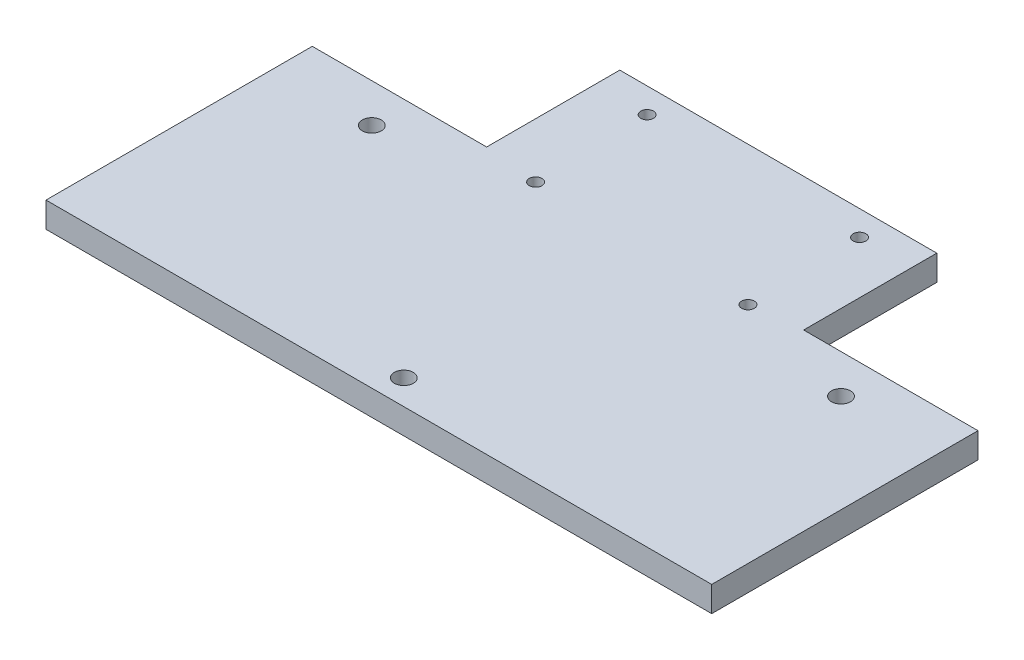
SolidWorks part; units mm, degrees
ref_plane "Front Plane" through (0, 0, 0) normal (0, 0, 1) x (1, 0, 0)
ref_plane "Top Plane" through (0, 0, 0) normal (0, 1, 0) x (1, 0, 0)
ref_plane "Right Plane" through (0, 0, 0) normal (1, 0, 0) x (0, 0, -1)
sketch "Sketch1" plane through (0, 0, 0) normal (0, 1, 0) x (1, 0, 0)
  line L0 (-47.6178, 3.1383) -> (57.3822, 3.1383) construction
  line L1 (-47.6178, 13.1383) -> (-20.1178, 13.1383)
  line L2 (-47.6178, 13.1383) -> (-47.6178, -28.8617)
  line L3 (-47.6178, -28.8617) -> (57.3822, -28.8617)
  line L4 (57.3822, 13.1383) -> (57.3822, -28.8617)
  line L5 (-47.6178, -18.8617) -> (57.3822, -18.8617) construction
  line L6 (-47.6178, -7.8617) -> (57.3822, -7.8617) construction
  line L7 (4.8822, 11.1383) -> (4.8822, -28.8617) construction
  line L8 (-20.1178, 13.1383) -> (-20.1178, 34.1383)
  line L9 (-20.1178, 34.1383) -> (29.8822, 34.1383)
  line L10 (29.8822, 34.1383) -> (29.8822, 13.1383)
  line L11 (29.8822, 13.1383) -> (57.3822, 13.1383)
  line L12 (4.8822, 34.1383) -> (4.8822, 11.1383) construction
  circle A0 centre (-32.1178, 7.0284) radius 1.5
  circle A1 centre (41.8822, 7.0284) radius 1.5
  circle A2 centre (4.8822, -24.9268) radius 1.5
  circle A3 centre (-11.8678, 30.2027) radius 1
  circle A4 centre (21.6322, 30.2027) radius 1
  circle A5 centre (-11.4651, 12.2072) radius 1
  circle A6 centre (22.0349, 12.2072) radius 1
  point P31 (21.6322, 30.2027)
  point P32 (0, 0)
  point P33 (0, 0)
  dimension "D5" = 37
  dimension "D6" = 3
  dimension "D7" = 50
  dimension "D8" = 2
  dimension "D11" = 21
  dimension "D1" = 105
  dimension "D2" = 42
  dimension "D3" = 22
  dimension "D4" = 11
  dimension "D9" = 33.5
  dimension "D10" = 18
  dimension "D12" = 33.5
extrude "Boss-Extrude1" add sketch "Sketch1" along normal blind 4
